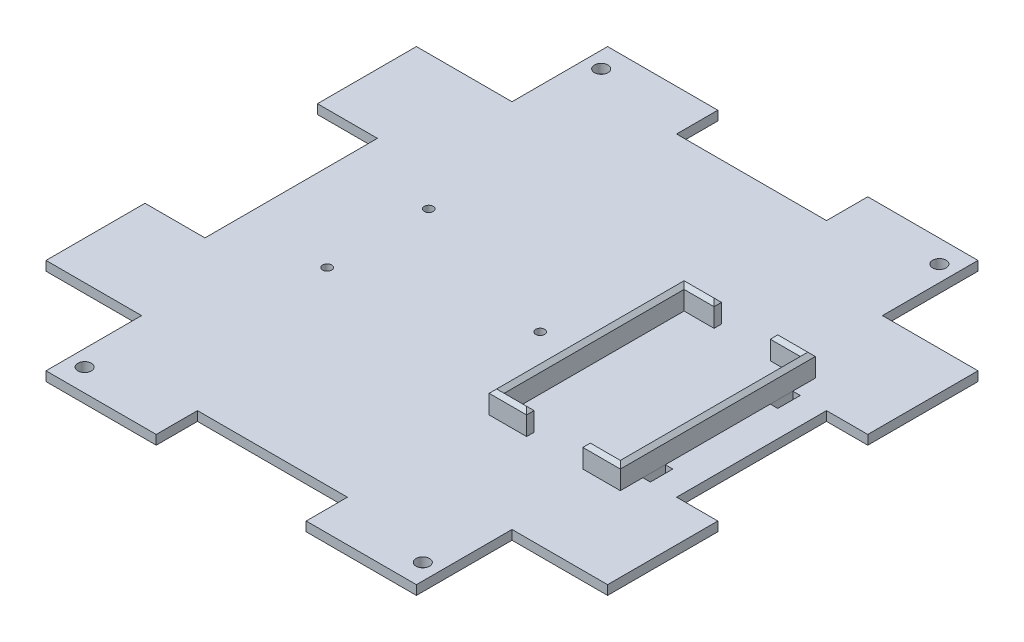
SolidWorks part; units mm, degrees
ref_plane "Front Plane" through (0, 0, 0) normal (0, 0, 1) x (1, 0, 0)
ref_plane "Top Plane" through (0, 0, 0) normal (0, 1, 0) x (1, 0, 0)
ref_plane "Right Plane" through (0, 0, 0) normal (1, 0, 0) x (0, 0, -1)
sketch "Sketch1" plane through (0, 0, 0) normal (0, 1, 0) x (1, 0, 0)
  line L0 (-62.2282, -68.317) -> (-29.8462, -68.317)
  line L1 (-29.8462, -68.317) -> (-29.8462, -100.699)
  line L2 (-29.8462, -100.699) -> (95.6398, -100.699)
  line L3 (95.6398, -100.699) -> (95.6398, -68.317)
  line L4 (95.6398, -68.317) -> (128.0218, -68.317)
  line L5 (128.0218, -68.317) -> (128.0218, 57.169)
  line L6 (128.0218, 57.169) -> (95.6398, 57.169)
  line L7 (95.6398, 57.169) -> (95.6398, 89.551)
  line L8 (95.6398, 89.551) -> (-29.8462, 89.551)
  line L9 (-29.8462, 89.551) -> (-29.8462, 57.169)
  line L10 (-29.8462, 57.169) -> (-62.2282, 57.169)
  line L11 (-62.2282, 57.169) -> (-62.2282, -68.317)
  dimension "D1" = 32.382
  dimension "D2" = 190.25
  dimension "D3" = 190.25
extrude "Boss-Extrude1" add sketch "Sketch1" along normal blind 3.175
sketch "Sketch2" plane through (0, 3.175, 0) normal (0, 1, 0) x (1, 0, 0)
  line L0 (-29.8462, -100.699) -> (95.6398, -100.699) construction
  line L1 (-29.8462, -68.317) -> (-29.8462, -100.699) construction
  line L2 (95.6398, 89.551) -> (-29.8462, 89.551) construction
  line L3 (95.6398, 57.169) -> (95.6398, 89.551) construction
  circle A0 centre (-24.3852, 81.931) radius 2.286
  circle A1 centre (90.1788, 81.931) radius 2.286
  circle A2 centre (90.1788, -93.079) radius 2.286
  circle A3 centre (-24.3852, -93.079) radius 2.286
  dimension "D1" = 4.572
  dimension "D2" = 7.62
  dimension "D3" = 5.461
  dimension "D4" = 7.62
  dimension "D5" = 5.461
extrude "Cut-Extrude1" cut sketch "Sketch2" against normal through all
sketch "Sketch3" plane through (0, 3.175, 0) normal (0, 1, 0) x (1, 0, 0)
  line L0 (-62.2282, 57.169) -> (-62.2282, -68.317) construction
  line L1 (-62.2282, -34.784) -> (-41.9082, -34.784)
  line L2 (-62.2282, -34.784) -> (-62.2282, 23.636)
  line L3 (-62.2282, 23.636) -> (-41.9082, 23.636)
  line L4 (-41.9082, -34.784) -> (-41.9082, 23.636)
  line L5 (95.6398, 89.551) -> (-29.8462, 89.551) construction
  line L6 (7.4968, 89.551) -> (58.2968, 89.551)
  line L7 (7.4968, 89.551) -> (7.4968, 75.581)
  line L8 (7.4968, 75.581) -> (58.2968, 75.581)
  line L9 (58.2968, 89.551) -> (58.2968, 75.581)
  line L10 (128.0218, -68.317) -> (128.0218, 57.169) construction
  line L11 (128.0218, 19.826) -> (114.0518, 19.826)
  line L12 (128.0218, 19.826) -> (128.0218, -30.974)
  line L13 (128.0218, -30.974) -> (114.0518, -30.974)
  line L14 (114.0518, 19.826) -> (114.0518, -30.974)
  line L15 (-29.8462, -100.699) -> (95.6398, -100.699) construction
  line L16 (58.2968, -100.699) -> (7.4968, -100.699)
  line L17 (58.2968, -100.699) -> (58.2968, -86.729)
  line L18 (58.2968, -86.729) -> (7.4968, -86.729)
  line L19 (7.4968, -100.699) -> (7.4968, -86.729)
  line L20 (95.6398, 89.551) -> (-29.8462, 89.551) construction
  line L21 (-62.2282, 57.169) -> (-62.2282, -68.317) construction
  point P26 (32.8968, 89.551)
  point P27 (32.8968, 75.581)
  point P28 (32.8968, -86.729)
  point P31 (-62.2282, -5.574)
  point P32 (-41.9082, -5.574)
  point P33 (114.0518, -5.574)
  dimension "D1" = 50.8
  dimension "D2" = 13.97
  dimension "D3" = 58.42
  dimension "D4" = 20.32
extrude "Cut-Extrude2" cut sketch "Sketch3" against normal through all
sketch "Sketch4" plane through (0, 3.175, 0) normal (0, 1, 0) x (1, 0, 0)
  line L0 (31.1161, -89.8283) -> (31.1161, 30.1717) construction
  line L1 (60.7118, 24.906) -> (70.8718, 24.906)
  line L2 (60.7118, 24.906) -> (60.7118, -36.054)
  line L3 (60.7118, -36.054) -> (70.8718, -36.054)
  line L4 (100.0818, 24.906) -> (100.0818, -36.054)
  line L5 (102.6218, 27.446) -> (102.6218, -38.594)
  line L6 (58.1718, -38.594) -> (70.8718, -38.594)
  line L7 (58.1718, 27.446) -> (58.1718, -38.594)
  line L8 (58.1718, 27.446) -> (70.8718, 27.446)
  line L9 (70.8718, 27.446) -> (70.8718, 24.906)
  line L10 (89.9218, 27.446) -> (89.9218, 24.906)
  line L11 (89.9218, 24.906) -> (100.0818, 24.906)
  line L12 (89.9218, 27.446) -> (102.6218, 27.446)
  line L13 (70.8718, -36.054) -> (70.8718, -38.594)
  line L14 (89.9218, -36.054) -> (89.9218, -38.594)
  line L15 (89.9218, -36.054) -> (100.0818, -36.054)
  line L16 (89.9218, -38.594) -> (102.6218, -38.594)
  line L17 (128.0218, -68.317) -> (128.0218, -30.974) construction
  line L20 (114.0518, 19.826) -> (114.0518, -30.974) construction
  point P21 (100.0818, -5.574)
  point P23 (0, 0)
  point P24 (0, 0)
  point P26 (114.0518, -5.574)
  dimension "D1" = 60.96
  dimension "D2" = 39.37
  dimension "D3" = 12.7
  dimension "D4" = 12.7
  dimension "D5" = 12.7
  dimension "D6" = 12.7
  dimension "D7" = 25.4
  dimension "D8" = 2.54
  dimension "D9" = 2.54
  dimension "D10" = 2.54
  dimension "D11" = 2.54
  dimension "D12" = 2.54
  dimension "D13" = 12.7
extrude "Boss-Extrude2" add sketch "Sketch4" along normal blind 7.62 separate body
chamfer "Chamfer1" distance 1.27 angle 45 8 edges at (65.7918, 10.795, 36.054) (70.8718, 10.795, 37.324) (64.5218, 10.795, 38.594) (58.1718, 10.795, 5.574) (64.5218, 10.795, -27.446) (70.8718, 10.795, -26.176) (65.7918, 10.795, -24.906) (60.7118, 10.795, 5.574)
chamfer "Chamfer2" distance 1.27 angle 45 8 edges at (100.0818, 10.795, 5.574) (95.0018, 10.795, -24.906) (89.9218, 10.795, -26.176) (96.2718, 10.795, -27.446) (102.6218, 10.795, 5.574) (96.2718, 10.795, 38.594) (89.9218, 10.795, 37.324) (95.0018, 10.795, 36.054)
sketch "Sketch5" plane through (0, 3.175, 0) normal (0, 1, 0) x (1, 0, 0)
  line L0 (58.1718, -38.594) -> (58.1718, 27.446) construction
  line L1 (58.1718, 19.826) -> (55.6318, 19.826)
  line L2 (58.1718, 19.826) -> (58.1718, 12.206)
  line L3 (58.1718, 12.206) -> (55.6318, 12.206)
  line L4 (55.6318, 19.826) -> (55.6318, 12.206)
  line L5 (102.6218, 27.446) -> (102.6218, -38.594) construction
  line L6 (58.1718, -30.974) -> (55.6318, -30.974)
  line L7 (58.1718, -30.974) -> (58.1718, -23.354)
  line L8 (58.1718, -23.354) -> (55.6318, -23.354)
  line L9 (55.6318, -30.974) -> (55.6318, -23.354)
  line L10 (102.6218, -30.974) -> (105.1618, -30.974)
  line L11 (102.6218, -30.974) -> (102.6218, -23.354)
  line L12 (102.6218, -23.354) -> (105.1618, -23.354)
  line L13 (105.1618, -30.974) -> (105.1618, -23.354)
  line L14 (58.1718, 27.446) -> (70.8718, 27.446) construction
  line L15 (102.6218, 12.206) -> (105.1618, 12.206)
  line L16 (102.6218, 12.206) -> (102.6218, 19.826)
  line L17 (102.6218, 19.826) -> (105.1618, 19.826)
  line L18 (105.1618, 12.206) -> (105.1618, 19.826)
  line L19 (70.8718, -38.594) -> (58.1718, -38.594) construction
  line L20 (102.6218, -38.594) -> (89.9218, -38.594) construction
  line L21 (89.9218, 27.446) -> (102.6218, 27.446) construction
  dimension "D1" = 2.54
  dimension "D2" = 7.62
  dimension "D3" = 7.62
  dimension "D4" = 7.62
  dimension "D5" = 7.62
  dimension "D6" = 7.62
extrude "Cut-Extrude3" cut sketch "Sketch5" against normal through all
sketch "Sketch6" plane through (0, 3.175, 0) normal (0, 1, 0) x (1, 0, 0)
  line L0 (-16.5082, 19.624) -> (46.814, 19.624) construction
  line L1 (46.814, 19.624) -> (46.814, -30.7721) construction
  line L2 (46.814, -30.7721) -> (-16.5082, -30.7721) construction
  line L3 (-16.5082, -30.7721) -> (-16.5082, 19.624) construction
  line L4 (-41.9082, -34.784) -> (-41.9082, 23.636) construction
  line L5 (-62.2282, 57.169) -> (-62.2282, 23.636) construction
  line L6 (-12.5082, -22.7825) -> (-12.5082, 11.6345) construction
  circle A0 centre (42.4452, -5.574) radius 1.524
  circle A1 centre (-12.5082, -22.7825) radius 1.524
  circle A2 centre (-12.5082, 11.6345) radius 1.524
  point P2 (-16.5082, -5.574)
  point P7 (-41.9082, -5.574)
  point P16 (-12.5082, -5.574)
  dimension "D7" = 3.048
  dimension "D1" = 63.3222
  dimension "D2" = 50.3961
  dimension "D3" = 45.72
  dimension "D4" = 4.3688
  dimension "D5" = 34.417
  dimension "D6" = 4
extrude "Cut-Extrude4" cut sketch "Sketch6" against normal blind 8.89
